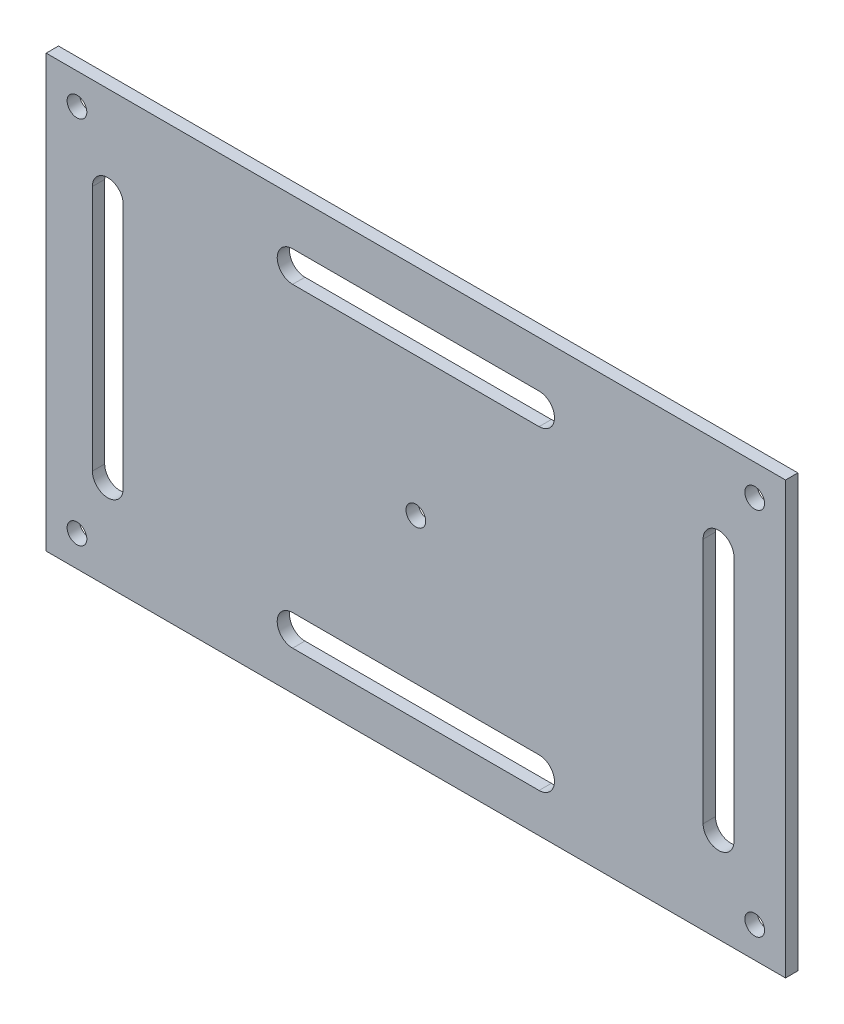
SolidWorks part; units mm, degrees
ref_plane "Front Plane" through (0, 0, 0) normal (0, 0, 1) x (1, 0, 0)
ref_plane "Top Plane" through (0, 0, 0) normal (0, 1, 0) x (1, 0, 0)
ref_plane "Right Plane" through (0, 0, 0) normal (1, 0, 0) x (0, 0, -1)
sketch "Sketch1" plane through (0, 0, 0) normal (0, 0, 1) x (1, 0, 0)
  line L0 (-53.4, 30) -> (-55, 30)
  line L1 (60, 35) -> (-60, 35)
  line L2 (60, 35) -> (60, -35)
  line L3 (60, -35) -> (-60, -35)
  line L4 (-60, 35) -> (-60, -35)
  line L5 (0, -35) -> (0, 35) construction
  line L6 (60, 0) -> (-60, 0) construction
  line L7 (55, 30) -> (53.4, 30)
  line L8 (55, 30) -> (55, 28.4)
  line L9 (55, -30) -> (53.4, -30)
  line L10 (-55, 30) -> (-55, 28.4)
  line L11 (0, -30) -> (0, 30) construction
  line L12 (55, 0) -> (-55, 0) construction
  line L13 (-55, -28.4) -> (-55, -30)
  line L14 (55, -28.4) -> (55, -30)
  line L15 (-53.4, -30) -> (-55, -30)
  line L16 (-60, 0) -> (-50, 0) construction
  line L17 (-20, 25) -> (20, 25) construction
  line L18 (0, 35) -> (0, 20) construction
  line L19 (-20, 27.5) -> (20, 27.5)
  line L20 (-20, 22.5) -> (20, 22.5)
  line L21 (-50, 20) -> (-50, -20) construction
  line L22 (-47.5, 20) -> (-47.5, -20)
  line L23 (-52.5, 20) -> (-52.5, -20)
  line L24 (-20, -26.1362) -> (20, -26.1362) construction
  line L25 (-20, -23.6362) -> (20, -23.6362)
  line L26 (-20, -28.6362) -> (20, -28.6362)
  line L27 (49.1289, 20) -> (49.1289, -20) construction
  line L28 (51.6289, 20) -> (51.6289, -20)
  line L29 (46.6289, 20) -> (46.6289, -20)
  circle A0 centre (-55, 30) radius 1.6
  circle A1 centre (-55, -30) radius 1.6
  circle A2 centre (55, -30) radius 1.6
  circle A3 centre (55, 30) radius 1.6
  circle A4 centre (0, 0) radius 1.6
  arc A5 (-20, 27.5) -> (-20, 22.5) centre (-20, 25) ccw
  arc A6 (20, 22.5) -> (20, 27.5) centre (20, 25) ccw
  arc A7 (-47.5, 20) -> (-52.5, 20) centre (-50, 20) ccw
  arc A8 (-52.5, -20) -> (-47.5, -20) centre (-50, -20) ccw
  arc A9 (-20, -23.6362) -> (-20, -28.6362) centre (-20, -26.1362) ccw
  arc A10 (20, -28.6362) -> (20, -23.6362) centre (20, -26.1362) ccw
  arc A11 (51.6289, 20) -> (46.6289, 20) centre (49.1289, 20) ccw
  arc A12 (46.6289, -20) -> (51.6289, -20) centre (49.1289, -20) ccw
  point P0 (0, 0)
  point P4 (0, 0)
  point P24 (0, 25)
  point P33 (-50, 0)
  point P40 (0, -26.1362)
  point P47 (49.1289, 0)
  dimension "D5" = 10
  dimension "D1" = 120
  dimension "D2" = 70
  dimension "D3" = 110
  dimension "D4" = 60
  dimension "D6" = 10
extrude "Boss-Extrude1" add sketch "Sketch1" along normal blind 2 contours L1 L4 L3 L2 A12 L29 A11 L28 A10 L26 A9 L25 A8 L23 A7 L22 A6 L20 A5 L19 A4 A3 A2 A1 A0 region at (58.6108, 0, 0)
